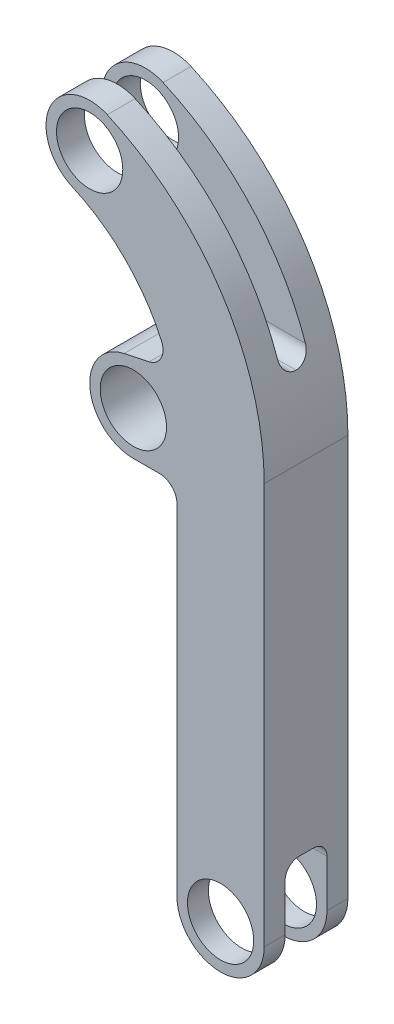
SolidWorks part; units mm, degrees
ref_plane "Alzado" through (0, 0, 0) normal (0, 0, 1) x (1, 0, 0)
ref_plane "Planta" through (0, 0, 0) normal (0, 1, 0) x (1, 0, 0)
ref_plane "Vista lateral" through (0, 0, 0) normal (1, 0, 0) x (0, 0, -1)
sketch "Croquis2" plane through (0, 0, 0) normal (0, 0, 1) x (1, 0, 0)
  line L0 (0, 115) -> (0, 0) construction
  line L1 (-12.5, 0) -> (-12.5, 97.5)
  line L2 (12.5, 0) -> (12.5, 115)
  line L3 (-142.407, 115) -> (142.407, 115) construction
  line L4 (-25, 102.5) -> (-17.5, 102.5)
  line L5 (0, 0) -> (-25, 115) construction
  line L6 (-25, 115) -> (-57.6336, 265.1147) construction
  line L7 (-37.5333, 212.7598) -> (-37.5333, 115) construction
  line L8 (-27.6554, 127.2147) -> (-20.4397, 128.7833)
  circle A0 centre (0, 0) radius 12.5
  circle A1 centre (0, 0) radius 9.5
  circle A2 centre (-25, 115) radius 12.5
  circle A3 centre (-25, 115) radius 9.5
  circle A4 centre (-37.5333, 172.6534) radius 12.5
  circle A5 centre (-37.5333, 172.6534) radius 9.5
  arc A6 (-16.9412, 135.7187) -> (-42.5916, 161.2226) centre (-63.0454, 115.0005) ccw
  arc A7 (-12.7466, 58.6344) -> (-12.5, 58.8554) centre (-63.0454, 115.0005) ccw
  arc A8 (12.5, 115) -> (-32.4751, 184.0842) centre (-63.0454, 115.0005) ccw
  arc A9 (-12.5, 97.5) -> (-17.5, 102.5) centre (-17.5, 97.5) ccw
  arc A10 (-16.9412, 135.7187) -> (-20.4397, 128.7833) centre (-21.5019, 133.6692) cw
  dimension "D1" = 25
  dimension "D2" = 19
  dimension "D4" = 19
  dimension "D3" = 25
  dimension "D8" = 19
  dimension "D9" = 25
  dimension "D11" = 5
  dimension "D5" = 115
  dimension "D6" = 25
  dimension "D7" = 0
  dimension "D10" = 59
  dimension "D12" = 0
  dimension "D13" = 0
  dimension "D14" = 0.001
extrude "Saliente-Extruir1" add sketch "Croquis2" along normal blind 24 contours A4 A5 | A6 A10 L8 A2 L4 A9 L1 A0 L2 A8 A4 | A2 A3 | A0 A1 region at (-3.7362, 93.5955, 0) region at (0, 12.1464, 0) region at (-27.354, 179.2804, 0) region at (-37.0769, 113.7024, 0)
sketch "Croquis5" plane through (-12.5, 0, 0) normal (-1, 0, 0) x (0, 0, 1)
  line L0 (24, 185.1534) -> (0, 185.1534) construction
  line L1 (8, 185.1534) -> (16, 185.1534)
  line L2 (8, 185.1534) -> (8, 135.7187)
  line L3 (8, 135.7187) -> (16, 135.7187)
  line L4 (16, 185.1534) -> (16, 135.7187)
  line L5 (24, 135.7187) -> (0, 135.7187) construction
  line L6 (24, 161.2226) -> (24, 185.1534) construction
  dimension "D1" = 8
  dimension "D2" = 8
extrude "Cortar-Extruir3" cut sketch "Croquis5" against normal through all both and the other way through all
sketch "Croquis6" plane through (-12.5, 0, 0) normal (-1, 0, 0) x (0, 0, 1)
  line L0 (0, -12.5) -> (24, -12.5) construction
  line L1 (18, -12.5) -> (6, -12.5)
  line L2 (18, -12.5) -> (18, 17.5)
  line L3 (18, 17.5) -> (6, 17.5)
  line L4 (6, -12.5) -> (6, 17.5)
  line L5 (0, 0) -> (0, -12.5) construction
  line L6 (24, -12.5) -> (24, 0) construction
  point P8 (0, -6.25)
  dimension "D1" = 30
  dimension "D2" = 6
  dimension "D3" = 6
extrude "Cortar-Extruir4" cut sketch "Croquis6" against normal through all both and the other way through all
sketch "Croquis7" plane through (0, 135.7187, 0) normal (0, 1, 0) x (1, 0, 0)
  line L0 (-32.4751, -16) -> (-50.0333, -16) construction
  line L1 (-50.0333, -8) -> (-35.5, -8)
  line L2 (-50.0333, -8) -> (-50.0333, -16)
  line L3 (-50.0333, -16) -> (-35.5, -16)
  line L4 (-35.5, -8) -> (-35.5, -16)
  line L5 (-37.5, 0) -> (-37.5, -24) construction
  dimension "D1" = 2
extrude "Cortar-Extruir5" cut sketch "Croquis7" against normal through all both and the other way through all
fillet "Redondeo1" radius 4 4 edges at (-3.6689, 135.7187, 16) (-3.6689, 135.7187, 8) (0, 17.5, 6) (0, 17.5, 18)
